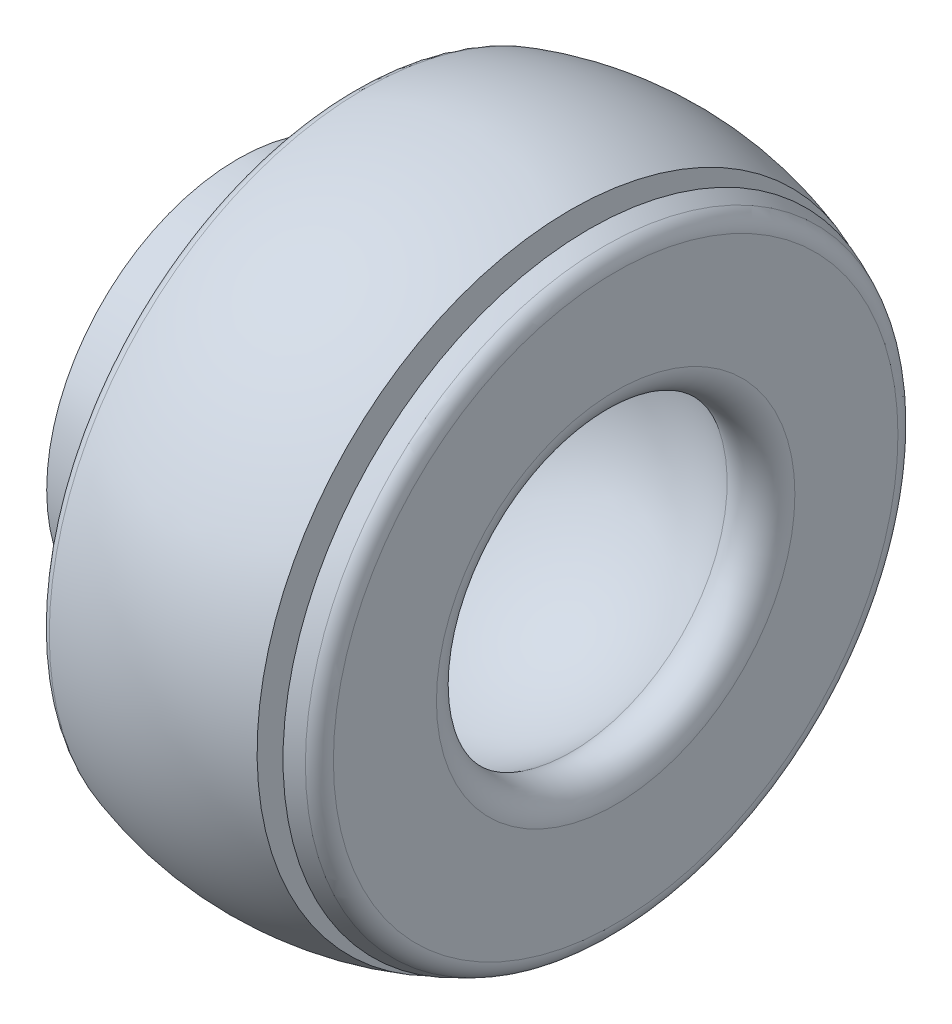
SolidWorks part; units mm, degrees
ref_plane "Face" through (0, 0, 0) normal (0, 0, 1) x (1, 0, 0)
ref_plane "Dessus" through (0, 0, 0) normal (0, 1, 0) x (1, 0, 0)
ref_plane "Droite" through (0, 0, 0) normal (1, 0, 0) x (0, 0, -1)
sketch "Esquisse1" plane through (0, 0, 0) normal (0, 0, 1) x (1, 0, 0)
  line L0 (-16.6495, 0) -> (17.0476, 0) construction
  line L1 (-6, 5.0583) -> (-6, 4.6167)
  line L2 (4, 7.4708) -> (4, 4.7434)
  line L3 (-3, 7.8621) -> (-3, 6.9265)
  line L4 (-3, 5.5) -> (-1.9422, 5.5)
  line L5 (-2.8, 6.7265) -> (-1.9422, 6.7265)
  line L6 (3.3, 8.1039) -> (3.3, 6.1132)
  line L7 (2.8, 8.2899) -> (2.8, 6.1132)
  line L8 (-3.4173, 4.0858) -> (-6, 4.6167)
  line L9 (-6, 5.0583) -> (-3, 5.5)
  arc A0 (2.8261, 4.1247) -> (-2.68, 4.2211) centre (0, 0) ccw
  arc A1 (3.7121, 7.9236) -> (3.3, 8.1039) centre (0, 0) ccw
  arc A2 (-1.9422, 6.7265) -> (-1.9422, 5.5) centre (-1.9422, 6.1132) cw
  arc A3 (2.8, 6.1132) -> (3.3, 6.1132) centre (3.05, 6.1132) ccw
  arc A4 (2.8, 8.2899) -> (-2.6515, 8.3386) centre (0, 0) ccw
  arc A5 (4, 4.7434) -> (2.8261, 4.1247) centre (3.25, 4.7434) cw
  arc A6 (-3.4173, 4.0858) -> (-2.68, 4.2211) centre (-3.216, 5.0653) ccw
  arc A7 (-2.6515, 8.3386) -> (-3, 7.8621) centre (-2.5, 7.8621) ccw
  arc A8 (4, 7.4708) -> (3.7121, 7.9236) centre (3.5, 7.4708) ccw
  arc A9 (-2.8, 6.7265) -> (-3, 6.9265) centre (-2.8, 6.9265) cw
  dimension "D1" = 10
  dimension "D2" = 17.5
  dimension "D9" = 0.75
  dimension "D10" = 1
  dimension "D11" = 0.5
  dimension "D12" = 0.2
  dimension "D3" = 4
  dimension "D4" = 10
  dimension "D5" = 7
  dimension "D6" = 5.5
  dimension "D7" = 0.7
  dimension "D8" = 0.5
revolve "Base-Révolution" add sketch "Esquisse1" angle 360 about L0
ref_axis "Axe1" through (-6, 0, 0) along (1, 0, 0)
ref_point "Point1"
ref_point "Point2"
